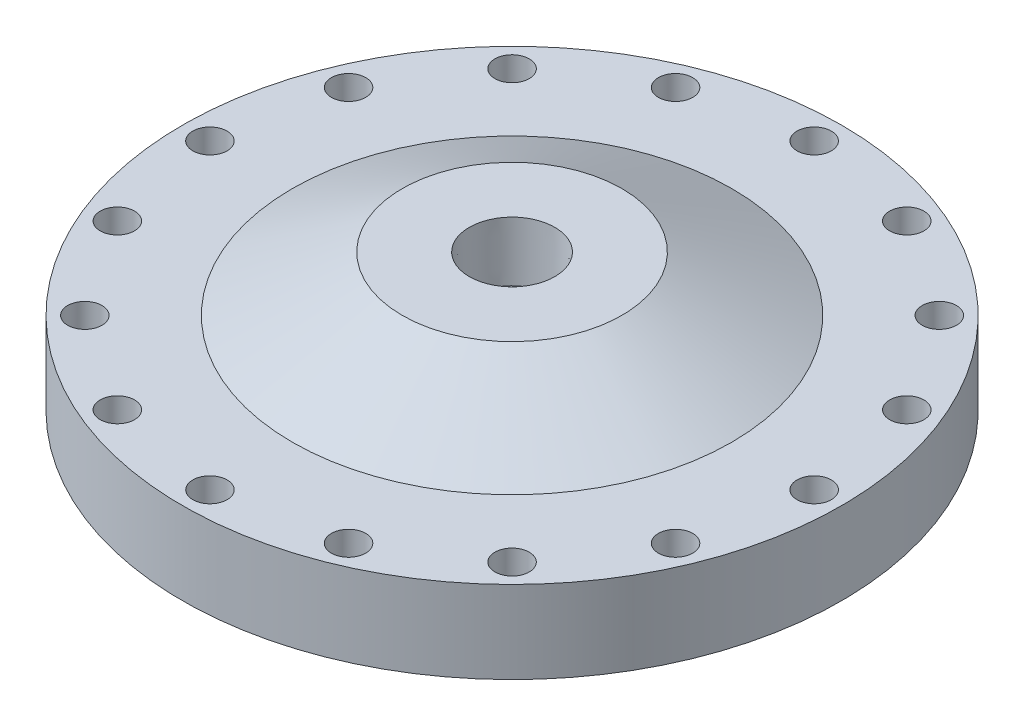
SolidWorks part; units mm, degrees
material "6061-T4 (SS)"
ref_plane "Front Plane" through (0, 0, 0) normal (0, 0, 1) x (1, 0, 0)
ref_plane "Top Plane" through (0, 0, 0) normal (0, 1, 0) x (1, 0, 0)
ref_plane "Right Plane" through (0, 0, 0) normal (1, 0, 0) x (0, 0, -1)
sketch "Sketch1" plane through (0, 0, 0) normal (0, 0, 1) x (1, 0, 0)
  line L0 (-76.2, -12.7) -> (-76.2, -31.75)
  line L1 (-76.2, -31.75) -> (-42.8625, -31.75)
  line L2 (0, -19.05) -> (0, 0)
  line L3 (-50.8, -12.7) -> (-76.2, -12.7)
  line L4 (-50.8, -12.7) -> (-25.4, 0)
  line L5 (-25.4, 0) -> (0, 0)
  line L7 (-42.8625, -31.75) -> (-15.875, -19.05)
  line L8 (-15.875, -19.05) -> (0, -19.05)
  dimension "D1" = 76.2
  dimension "D2" = 19.05
  dimension "D3" = 33.3375
  dimension "D4" = 25.4
  dimension "D5" = 25.4
  dimension "D6" = 15.875
  dimension "D7" = 19.05
  dimension "D8" = 31.75
revolve "Revolve1" add sketch "Sketch1" angle 360 about L2
hole_wizard "5/16 (0.3125) Diameter Hole1" positions "Sketch4" profile "Sketch5" hole size "5/16" standard "ANSI Inch"
sketch "Sketch4" plane through (0, -12.7, 0) normal (0, 1, 0) x (1, 0, 0)
  point P0 (-69.85, 0)
  dimension "D1" = 69.85
sketch "Sketch5" plane through (-69.85, -12.7, 0) normal (1, 0, 0) x (0, 0, 1)
  line L0 (0, 0) -> (0, 40.4847)
  line L1 (0, 40.4847) -> (3.9687, 38.1)
  line L2 (3.9687, 38.1) -> (3.9687, 0)
  line L5 (3.9687, 0) -> (0, 0)
  line L10 (0, 40.4847) -> (-3.9688, 38.1) construction
  line L11 (0, -6.35) -> (0, 107.95) construction
  dimension "Hole Dia." = 7.9375
  dimension "Hole Depth" = 38.1
  dimension "Drill Angle" = 118
ref_axis "Axis1" through (0, 0.635, 0) along (0, -1, 0)
pattern_circular "CirPattern1" count 16 over 360 about axis through (0, 0.635, 0) along (0, -1, 0) of "5/16 (0.3125) Diameter Hole1"
hole_wizard "1/2 NPT Tapped Hole1" positions "Sketch6" profile "Sketch8" size "1/2" standard "ANSI Inch" end condition up to next
sketch "Sketch6" plane through (0, 0, 0) normal (0, 1, 0) x (1, 0, 0)
  point P0 (0, 0)
sketch "Sketch8" plane through (0, 0, 0) normal (1, 0, 0) x (0, 0, 1)
  line L0 (0, 0) -> (0, 19.05)
  line L1 (0, 19.05) -> (8.9281, 19.05)
  line L2 (-9.4797, 13.462) -> (-9.8828, 0) construction
  line L3 (8.9281, 19.05) -> (8.9281, 13.462)
  line L4 (8.9281, 13.462) -> (9.4797, 13.462)
  line L5 (9.4797, 13.462) -> (9.8828, 0)
  line L7 (9.8828, 0) -> (0, 0)
  line L8 (0, -6.35) -> (0, 107.95) construction
  line L11 (-8.9281, 13.462) -> (-9.4797, 13.462) construction
  dimension "Thru Tap Drill Dia." = 17.8562
  dimension "Thru Tap Drill Depth" = 19.05
  dimension "Thread Dia." = 19.7656
  dimension "Thread Angle" = 3.43
  dimension "Thread Depth" = 13.462
cosmetic thread "Hole Thread1" parameters "D1"=13.462, "D2"=21.3288
